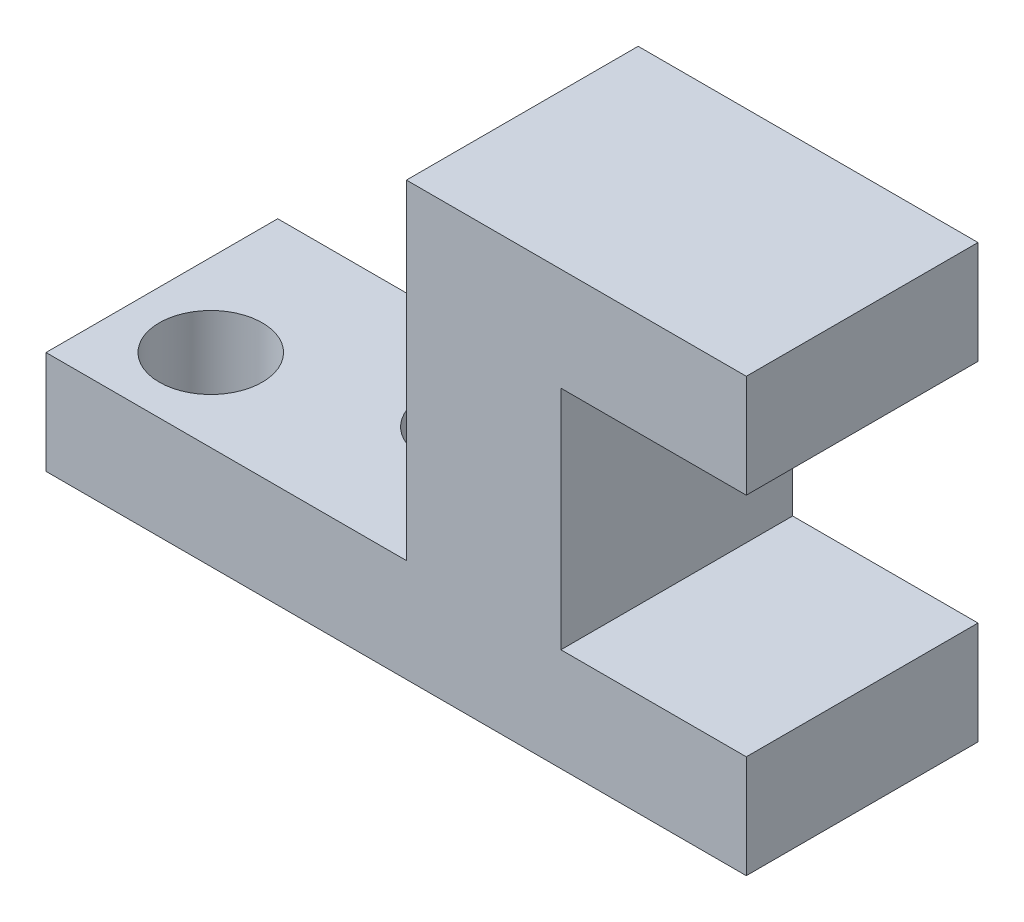
SolidWorks part; units mm, degrees
material "6061 Alloy"
ref_plane "Front Plane" through (0, 0, 0) normal (0, 0, 1) x (1, 0, 0)
ref_plane "Top Plane" through (0, 0, 0) normal (0, 1, 0) x (1, 0, 0)
ref_plane "Right Plane" through (0, 0, 0) normal (1, 0, 0) x (0, 0, -1)
sketch "Sketch1" plane through (0, 0, 0) normal (0, 0, 1) x (1, 0, 0)
  line L0 (0, 0) -> (-13.6, 0)
  line L1 (-13.6, 0) -> (-13.6, 2)
  line L2 (-13.6, 2) -> (-6.6, 2)
  line L3 (-6.6, 2) -> (-6.6, 8.4)
  line L4 (-6.6, 8.4) -> (0, 8.4)
  line L5 (0, 8.4) -> (0, 6.4)
  line L6 (0, 6.4) -> (-3.6, 6.4)
  line L7 (-3.6, 6.4) -> (-3.6, 2)
  line L8 (-3.6, 2) -> (0, 2)
  line L9 (0, 2) -> (0, 0)
  dimension "D1" = 2
  dimension "D2" = 2
  dimension "D3" = 3
  dimension "D4" = 3.6
  dimension "D5" = 4.4
  dimension "D6" = 7
extrude "Boss-Extrude1" add sketch "Sketch1" along normal blind 4.5
sketch "Sketch2" plane through (0, 2, 0) normal (0, 1, 0) x (1, 0, 0)
  line L0 (-6.6, -4.5) -> (-13.6, -4.5) construction
  line L1 (-6.6, 0) -> (-13.6, 0) construction
  line L2 (-13.6, -4.5) -> (-13.6, 0) construction
  line L3 (-6.6, -4.5) -> (-6.6, 0) construction
  circle A0 centre (-8.2, -1.6) radius 1
  circle A1 centre (-12, -2.9) radius 1
  dimension "D1" = 2
  dimension "D2" = 2
  dimension "D3" = 1.6
  dimension "D4" = 1.6
  dimension "D5" = 1.6
  dimension "D6" = 1.6
extrude "Cut-Extrude1" cut sketch "Sketch2" against normal blind 10
